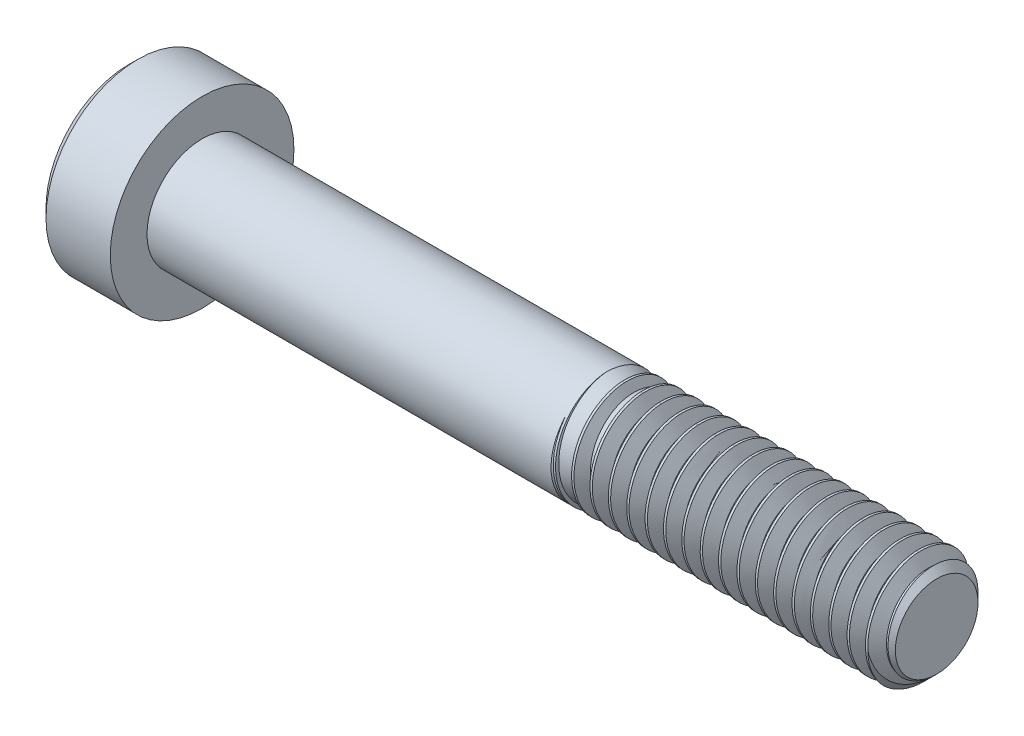
SolidWorks part; units mm, degrees
ref_plane "Front Plane" through (0, 0, 0) normal (0, 0, 1) x (1, 0, 0)
ref_plane "Top Plane" through (0, 0, 0) normal (0, 1, 0) x (1, 0, 0)
ref_plane "Right Plane" through (0, 0, 0) normal (1, 0, 0) x (0, 0, -1)
sketch "Sketch1" plane through (0, 0, 0) normal (0, 0, 1) x (1, 0, 0)
  line L0 (20, 0) -> (-20, 0) construction
  line L1 (20, 3) -> (20, -3) construction
  line L2 (-20, 5) -> (-20, -5) construction
  line L3 (-20, 5) -> (-23.5, 5) construction
  line L4 (-23.5, 5) -> (-24, 4.5) construction
  line L5 (-24, 4.5) -> (-24, -4.5) construction
  line L6 (-24, -4.5) -> (-23.5, -5) construction
  line L7 (-23.5, -5) -> (-20, -5) construction
  line L8 (2, 3) -> (2, -3) construction
  line L9 (19.9375, 3.1083) -> (20.9375, 3.1083) construction
  line L10 (20.9375, 3.1083) -> (20.4375, 2.2422) construction
  line L11 (20.4375, 2.2422) -> (19.9375, 3.1083) construction
  line L12 (20.4375, 3.1083) -> (20.4375, 3) construction
  line L13 (20.4375, 2.2422) -> (20.4375, 2.3505) construction
  line L14 (20, 3) -> (20.875, 3) construction
  line L15 (20.375, 2.3505) -> (20.5, 2.3505)
  line L16 (19.9688, 3.0541) -> (20.9062, 3.0541)
  line L17 (20.9062, 3.0541) -> (20.5, 2.3505)
  line L18 (20.375, 2.3505) -> (19.9688, 3.0541)
  line L19 (-20.88, -2) -> (-20.88, 2)
  point P7 (-20.88, 0)
  point P12 (16.5, -3)
  point P24 (20.4375, 3)
  point P27 (20.4375, 2.3505)
  point P30 (20.4375, 3.0541)
  point P34 (-20.88, 0)
  dimension "D1" = 45
  dimension "Thread Size" = 6
  dimension "Length" = 40
  dimension "Head DiameterSketch1" = 10
  dimension "Head Height" = 4
  dimension "Hex Depth" = 3.12
  dimension "Chamfer" = 0.5
  dimension "D2" = 3.5
  dimension "Thread Pitch" = 1
  dimension "D3" = 0.125
  dimension "Drive Size" = 4
ref_plane "Plane1" through (20, 0, 0) normal (1, 0, 0) x (0, 0, -1)
ref_plane "Plane2" through (-24, 0, 0) normal (1, 0, 0) x (0, 0, -1)
sketch "Sketch2" plane through (20, 0, 0) normal (1, 0, 0) x (0, 0, -1)
  circle A0 centre (0, 0) radius 3
extrude "Boss-Extrude1" add sketch "Sketch2" against normal up to vertex (18 mm away) up to point (2, 3, 0)
sketch "Sketch3" plane through (20, 0, 0) normal (1, 0, 0) x (0, 0, -1)
  circle A0 centre (0, 0) radius 3 construction
  circle A1 centre (0, 0) radius 3
chamfer "Chamfer1" distance 0.75 angle 45 1 edges at (20, 0, -3)
sketch "Sketch4" plane through (-24, 0, 0) normal (1, 0, 0) x (0, 0, -1)
  line L0 (-5, 0.7937) -> (5, 0.7937) construction
  line L1 (0, 2.3094) -> (-2, 1.1547)
  line L2 (-2, 1.1547) -> (-2, -1.1547)
  line L3 (-2, -1.1547) -> (0, -2.3094)
  line L4 (0, -2.3094) -> (2, -1.1547)
  line L5 (2, -1.1547) -> (2, 1.1547)
  line L6 (2, 1.1547) -> (0, 2.3094)
  line L7 (0, 0) -> (0, 0.7937) construction
  circle A0 centre (0, 0) radius 2 construction
  dimension "D1" = 10
  dimension "D2" = 0.7937
sketch "Sketch10" plane through (0, 0, 0) normal (0, 0, 1) x (1, 0, 0)
  line L0 (-20, 0) -> (3.7321, 0) construction
  line L1 (3.7321, 0) -> (2, 3)
  line L2 (2, 3) -> (-20, 3)
  line L3 (-20, 3) -> (-20, 0)
  line L4 (-20, 5) -> (-20, -5) construction
  line L5 (-20, 0) -> (3.7321, 0)
  dimension "D1" = 60
revolve "Revolve2" add sketch "Sketch10" angle 360 about L0
sketch "Sketch6" plane through (0, 0, 0) normal (0, 0, 1) x (1, 0, 0)
  line L0 (-23.5, 5) -> (-24, 4.5) construction
  line L1 (-20, 5) -> (-23.5, 5) construction
  line L2 (-20, 5) -> (-20, -5) construction
  line L3 (-24, 4.5) -> (-24, -4.5) construction
  line L4 (-23.5, 5) -> (-24, 4.5)
  line L5 (-20, 5) -> (-23.5, 5)
  line L6 (-20, 5) -> (-20, 0)
  line L7 (-24, 4.5) -> (-24, 0)
  line L8 (-20, 0) -> (-24, 0) construction
  line L9 (-20, 0) -> (-24, 0)
revolve "Revolve1" add sketch "Sketch6" angle 360 about L8
extrude "Cut-Extrude1" cut sketch "Sketch4" along normal up to vertex (3.12 mm away) up to point (-20.88, 0, 0)
sketch "Sketch8" plane through (-24, 0, 0) normal (-1, 0, 0) x (0, 0, 1)
  circle A1 centre (0, 0) radius 2.3094
extrude "Cut-Extrude2" cut sketch "Sketch8" against normal through all draft 45
curve "Helix/Spiral1" pitch 1 height 19 turns 19 parameters "Pitch"=1
ref_plane "Plane3" through (2, 3, 0) normal (-1, 0, 0) x (0, 0, 1)
split "Split1" trim tools "Plane3" bodies to split 105 resulting bodies 108 109
sketch "Sketch5" plane through (0, 0, 0) normal (0, 0, 1) x (1, 0, 0)
  line L0 (19.9688, 3.0541) -> (20.9062, 3.0541) construction
  line L1 (20.375, 2.3505) -> (19.9688, 3.0541) construction
  line L2 (20.375, 2.3505) -> (20.5, 2.3505) construction
  line L3 (20.9062, 3.0541) -> (20.5, 2.3505) construction
  line L4 (19.9688, 3.0541) -> (20.9062, 3.0541)
  line L5 (20.375, 2.3505) -> (19.9688, 3.0541)
  line L6 (20.375, 2.3505) -> (20.5, 2.3505)
  line L7 (20.9062, 3.0541) -> (20.5, 2.3505)
sweep "Cut-Sweep1" cut profiles "Sketch5" path "Helix/Spiral1" align with end faces yes
sketch "Sketch11" plane through (2, 3, 0) normal (-1, 0, 0) x (0, 0, 1)
  line L0 (0, 0) -> (0, -6) construction
  circle A0 centre (0, -3) radius 3
extrude "Boss-Extrude2" add sketch "Sketch11" against normal blind 10 draft 20
equation "\"D3@Helix/Spiral1\" = \"Minimum Thread Length@Sketch1\" + \"Pitch@Helix/Spiral1\""
equation "\"D1@Chamfer1\" = \"Pitch@Helix/Spiral1\"*.75"
equation "\"D2@Sketch1\"=\"Pitch@Helix/Spiral1\"*3.5"
equation "\"D1@Sketch4\" = \"Head DiameterSketch1@Sketch1\""
equation "\"Chamfer@Sketch1\" = \"Head Height@Sketch1\"/8"
equation "\"D3@Sketch1\"=\"Thread Pitch@Sketch1\"/8"
equation "\"Pitch@Helix/Spiral1\"=\"Thread Pitch@Sketch1\""
